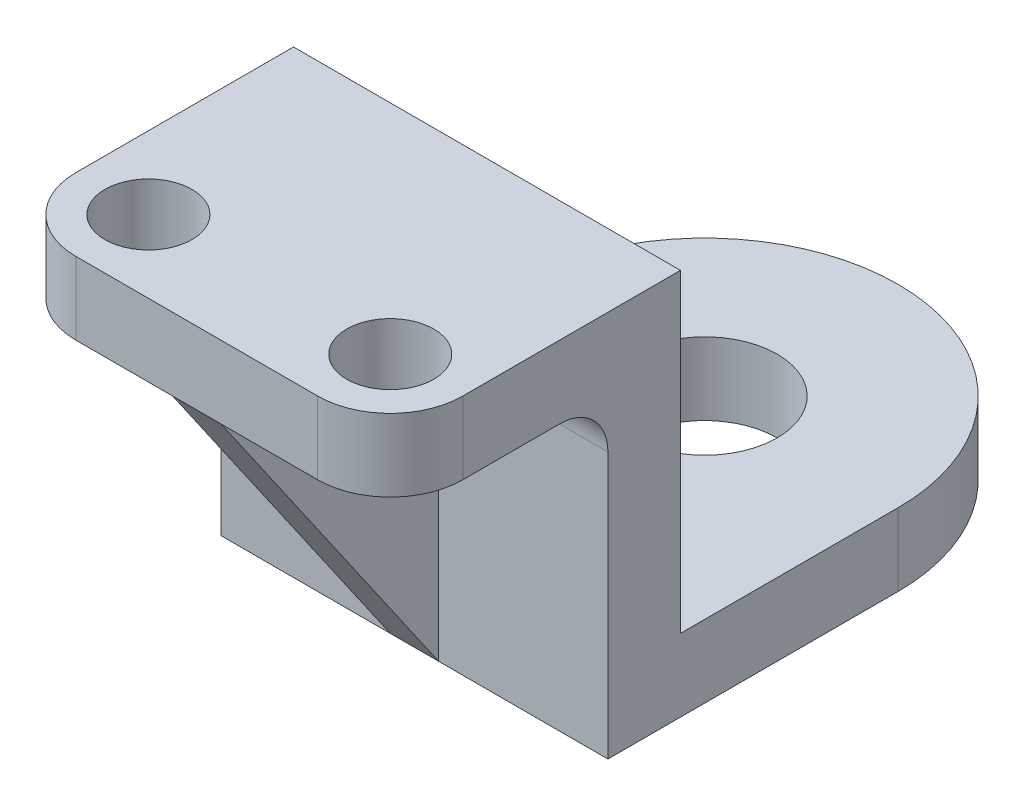
SolidWorks part; units mm, degrees
material "ABS"
ref_plane "Front Plane" through (0, 0, 0) normal (1, 0, 0) x (0, 1, 0)
ref_plane "Top Plane" through (0, 0, 0) normal (0, 0, 1) x (0, 1, 0)
ref_plane "Right Plane" through (0, 0, 0) normal (0, 1, 0) x (-1, 0, 0)
sketch "Sketch1" plane through (0, 0, 0) normal (1, 0, 0) x (0, 1, 0)
  line L0 (-65, 0) -> (-65, 85)
  line L1 (-65, 85) -> (0, 85)
  line L2 (0, 85) -> (0, 100)
  line L3 (0, 100) -> (-80, 100)
  line L4 (-80, 100) -> (-80, 0)
  line L5 (-80, 0) -> (-65, 0)
  point P9 (-50.2604, 70)
  dimension "D1" = 80
  dimension "D2" = 85
  dimension "D3" = 15
  dimension "D4" = 15
extrude "Boss-Extrude1" add sketch "Sketch1" along normal mid plane 80
sketch "Sketch2" plane through (0, 0, 0) normal (1, 0, 0) x (0, 1, 0)
  line L0 (-15, 145) -> (-15, 100)
  line L1 (0, 100) -> (-80, 100) construction
  line L2 (-15, 100) -> (0, 100)
  line L3 (0, 100) -> (0, 145)
  line L4 (0, 145) -> (-15, 145)
  line L5 (-65, 85) -> (0, 85) construction
  dimension "D1" = 15
  dimension "D2" = 60
  dimension "D3" = 15
extrude "Boss-Extrude2" add sketch "Sketch2" along normal mid plane 80
fillet "Fillet1" radius 15 2 edges at (40, -7.5, 145) (-40, -7.5, 145)
sketch "Sketch9" plane through (0, 0, 0) normal (0, 1, 0) x (-1, 0, 0)
  line L0 (0, 0) -> (0, 25.2277) construction
  circle A0 centre (25, 130) radius 9
  arc A2 (40, 130) -> (25, 145) centre (25, 130) ccw construction
  circle A3 centre (-25, 130) radius 9
  dimension "D1" = 18
extrude "Cut-Extrude1" cut sketch "Sketch9" against normal blind 80
fillet "Fillet2" radius 40 2 edges at (-40, -72.5, 0) (40, -72.5, 0)
sketch "Sketch11" plane through (0, -80, 0) normal (0, -1, 0) x (1, 0, 0)
  circle A0 centre (0, 40) radius 15
  circle A1 centre (25, 130) radius 9 construction
  dimension "D1" = 30
  dimension "D2" = 90
extrude "Cut-Extrude6" cut sketch "Sketch11" against normal through all both and the other way through all
fillet "Fillet3" radius 10 1 edges at (0, -15, 100)
sketch "Sketch14" plane through (0, 0, 0) normal (1, 0, 0) x (0, 1, 0)
  line L0 (-15, 145) -> (-80, 100)
rib "Rib17" sketch "Sketch14" sketch "Sketch14" thickness 10 extrusion direction parallel to sketch draft on no parameters "D1"=10
